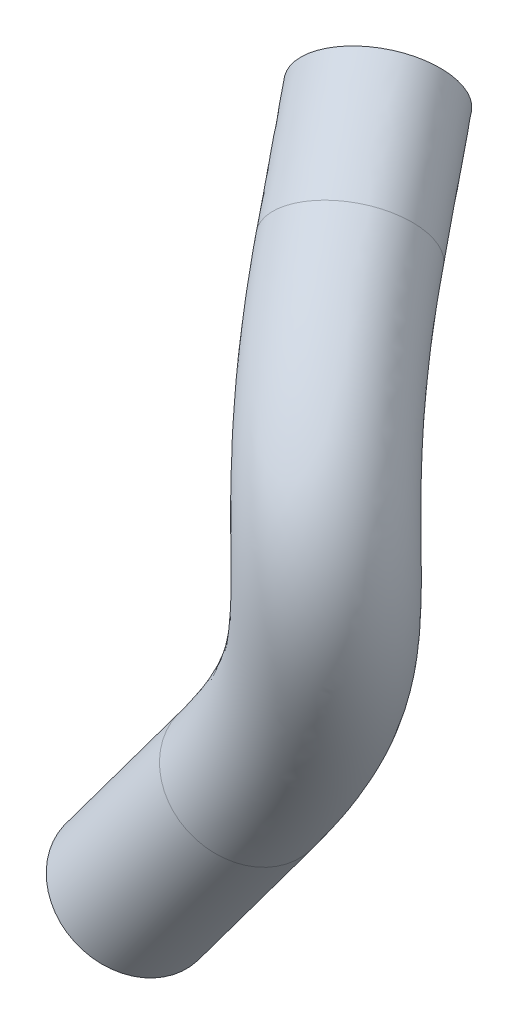
SolidWorks part; units mm, degrees
material "Silicon Rubber"
ref_plane "X-Y Datum" through (0, 0, 0) normal (0, 0, 1) x (1, 0, 0)
ref_plane "X-Z Datum" through (0, 0, 0) normal (0, 1, 0) x (1, 0, 0)
ref_plane "Y-Z Datum" through (0, 0, 0) normal (1, 0, 0) x (0, 0, -1)
sketch3d "3DSketch1"
  line L0 (202.8177, 305.3534, 24.6391) -> (225.5353, 335.9397, 24.6391)
  line L1 (229.5407, 421.9495, 7.7474) -> (216.3328, 432.7155, -11.0889)
  line L2 (229.5407, 421.9495, 7.7474) -> (216.3328, 432.7155, -11.0889) construction
  line L3 (229.0727, 422.3309, 7.08) -> (216.3328, 432.7155, -11.0889) construction
  line L4 (222.6956, 332.1164, 24.6391) -> (225.5353, 335.9397, 24.6391) construction
  circle A0 centre (222.6956, 332.1164, 24.6391) radius 12.3825 construction
  circle A4 centre (216.3328, 432.7155, -11.0889) radius 10 construction
  circle A5 centre (229.0727, 422.3309, 7.08) radius 7.8 construction
  circle A10 centre (225.5353, 335.9397, 24.6391) radius 6.985 construction
  circle A11 centre (216.3328, 432.7155, -11.0889) radius 10 construction
  circle A13 centre (229.0727, 422.3309, 7.08) radius 7.8 construction
  circle A14 centre (222.6956, 332.1164, 24.6391) radius 12.3825 construction
  circle A15 centre (225.5353, 335.9397, 24.6391) radius 6.985 construction
  spline S0 degree 3 poles (225.5353, 335.9397, 24.6391) (253.1388, 373.1042, 24.6391) (258.8505, 398.0582, 49.5476) (229.5407, 421.9495, 7.7474) knots 0 0 0 0 1 1 1 1
  point P6 (221.5328, 428.4769, -3.673)
  point P10 (233.1286, 419.0248, 12.8643)
  point P12 (221.5328, 428.4769, -3.673)
  point P14 (233.1286, 419.0248, 12.8643)
  point P16 (215.3124, 322.1759, 24.6391)
  point P19 (221.3704, 330.3322, 24.6391)
  point P21 (215.3124, 322.1759, 24.6391)
  point P24 (221.3704, 330.3322, 24.6391)
  dimension "D2" = 38.1
  dimension "D1" = 25.4
sweep "Sweep1" add path "3DSketch1" circular profile diameter 26.9875 parameters "D3"=26.9875
sweep "Cut-Sweep1" cut path "3DSketch1<2>" circular profile diameter 19.05 parameters "D3"=19.05
sketch3d "3DSketch1<2>" same geometry as "3DSketch1"
